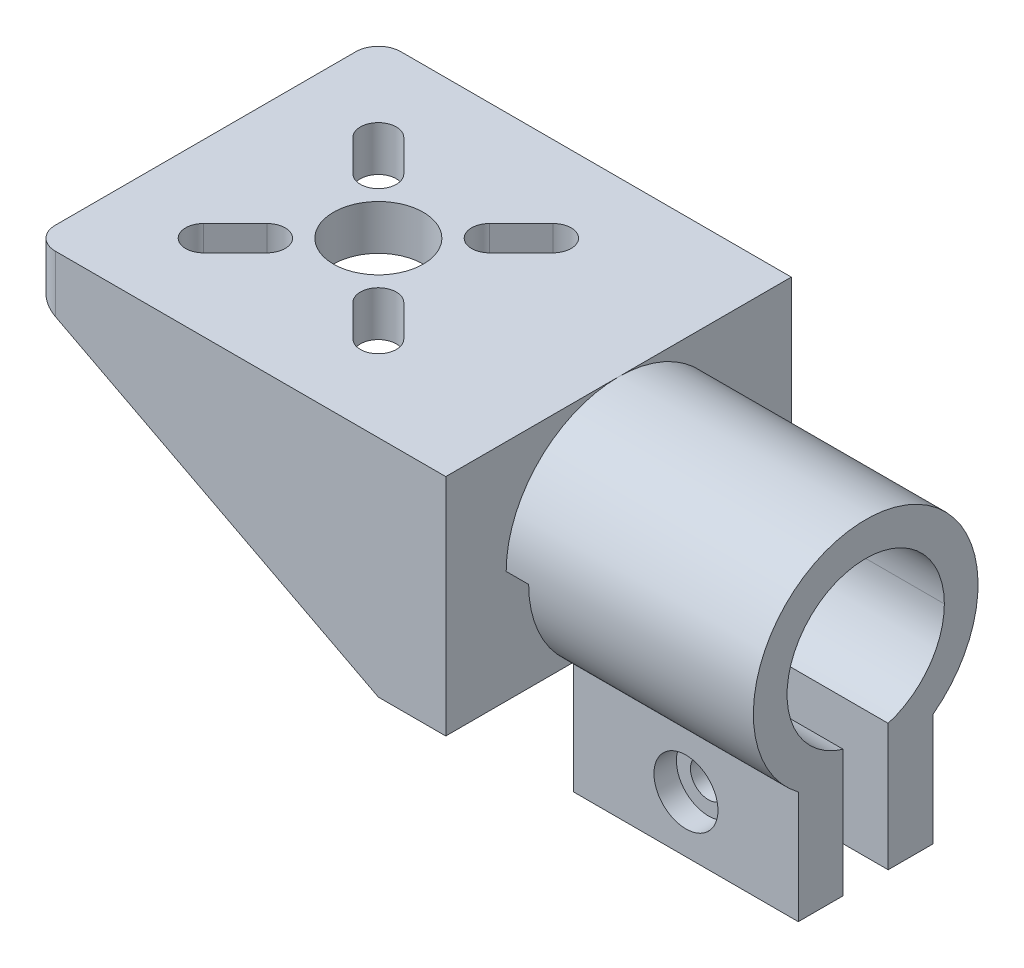
SolidWorks part; units mm, degrees
material "ABS"
ref_plane "Płaszczyzna przednia" through (0, 0, 0) normal (0, 0, 1) x (1, 0, 0)
ref_plane "Płaszczyzna górna" through (0, 0, 0) normal (0, 1, 0) x (1, 0, 0)
ref_plane "Płaszczyzna prawa" through (0, 0, 0) normal (1, 0, 0) x (0, 0, -1)
sketch "Szkic1" plane through (0, 0, 0) normal (0, 1, 0) x (1, 0, 0)
  line L0 (0, 0) -> (-4.9497, 4.9497) construction
  line L1 (-4.9497, 4.9497) -> (-7.7782, 7.7782) construction
  line L2 (-7.7782, 7.7782) -> (-4.9497, 4.9497) construction
  line L3 (-6.6468, 8.9095) -> (-3.8184, 6.0811)
  line L4 (-8.9095, 6.6468) -> (-6.0811, 3.8184)
  line L5 (7.7782, 7.7782) -> (4.9497, 4.9497) construction
  line L6 (8.9095, 6.6468) -> (6.0811, 3.8184)
  line L7 (6.6468, 8.9095) -> (3.8184, 6.0811)
  line L8 (7.7782, -7.7782) -> (4.9497, -4.9497) construction
  line L9 (6.6468, -8.9095) -> (3.8184, -6.0811)
  line L10 (8.9095, -6.6468) -> (6.0811, -3.8184)
  line L11 (-7.7782, -7.7782) -> (-4.9497, -4.9497) construction
  line L12 (-8.9095, -6.6468) -> (-6.0811, -3.8184)
  line L13 (-6.6468, -8.9095) -> (-3.8184, -6.0811)
  line L14 (0, 9) -> (0, -9) construction
  line L15 (-15.3782, 15.3782) -> (15.3782, 15.3782)
  line L16 (0, 0) -> (9.4723, 0) construction
  line L17 (-15.3782, -15.3782) -> (-15.3782, 15.3782)
  line L18 (15.3782, 15.3782) -> (15.3782, -15.3782)
  line L19 (15.3782, -15.3782) -> (-15.3782, -15.3782)
  circle A0 centre (0, 0) radius 4
  arc A10 (-6.6468, 8.9095) -> (-8.9095, 6.6468) centre (-7.7782, 7.7782) ccw
  arc A11 (-6.0811, 3.8184) -> (-3.8184, 6.0811) centre (-4.9497, 4.9497) ccw
  arc A12 (8.9095, 6.6468) -> (6.6468, 8.9095) centre (7.7782, 7.7782) ccw
  arc A13 (3.8184, 6.0811) -> (6.0811, 3.8184) centre (4.9497, 4.9497) ccw
  arc A14 (6.6468, -8.9095) -> (8.9095, -6.6468) centre (7.7782, -7.7782) ccw
  arc A15 (6.0811, -3.8184) -> (3.8184, -6.0811) centre (4.9497, -4.9497) ccw
  arc A16 (-8.9095, -6.6468) -> (-6.6468, -8.9095) centre (-7.7782, -7.7782) ccw
  arc A17 (-3.8184, -6.0811) -> (-6.0811, -3.8184) centre (-4.9497, -4.9497) ccw
  point P3 (-6.364, 6.364)
  point P13 (0, 0)
  point P14 (6.364, 6.364)
  point P21 (6.364, -6.364)
  point P22 (0, 0)
  point P29 (-6.364, -6.364)
  point P36 (0, 0)
  point P39 (0, -9)
  point P40 (0, 15.3782)
  point P45 (-15.3782, 0)
  dimension "D6" = 8
  dimension "D1" = 7
  dimension "D2" = 4
  dimension "D3" = 3.2
  dimension "D5" = 7.6
  dimension "D7" = 7.6
  dimension "D4" = 4
extrude "Dodanie-wyciągnięcie1" add sketch "Szkic1" along normal blind 4
ref_plane "Płaszczyzna1" through (15.3782, 0, 0) normal (1, 0, 0) x (0, 0, -1)
sketch "Szkic2" plane through (15.3782, 0, 0) normal (1, 0, 0) x (0, 0, -1)
  line L1 (0, -13) -> (0, -16) construction
  line L2 (-15.3782, -16) -> (15.3782, -16)
  line L3 (15.3782, -16) -> (15.3782, 4)
  line L4 (-15.3782, -16) -> (-15.3782, 4)
  line L8 (0, 4) -> (0, 1) construction
  line L9 (-15.3782, 4) -> (15.3782, 4) construction
  line L10 (-15.3782, 4) -> (15.3782, 4)
  circle A0 centre (0, -6) radius 7
  point P0 (0, -13)
  point P9 (0, -16)
  point P10 (0, -16)
  point P19 (0, 4)
  dimension "D1" = 14
  dimension "D2" = 3
  dimension "D3" = 3
extrude "Dodanie-wyciągnięcie2" add sketch "Szkic2" along normal blind 4 contours A0 | L4 L2 L3 A0 region at (15.3782, -6, 15.0113) region at (15.3782, -6, 0)
ref_plane "Płaszczyzna2" through (-3.2753, -6.2961, 0) normal (-0.4615, -0.8871, 0) x (-0.8871, 0.4615, 0)
sketch "Szkic5" plane through (-3.2753, -6.2961, 0) normal (-0.4615, -0.8871, 0) x (-0.8871, 0.4615, 0)
  line L0 (13.6426, -15.3782) -> (-21.0266, -15.3782)
  line L1 (-21.0266, -15.3782) -> (-21.0266, -12.3782)
  line L2 (-21.0266, -15.3782) -> (-21.0266, 15.3782) construction
  line L3 (-21.0266, -12.3782) -> (13.6426, -12.3782)
  line L4 (13.6426, 15.3782) -> (13.6426, -15.3782) construction
  line L5 (13.6426, -12.3782) -> (13.6426, -15.3782)
  dimension "D1" = 3
extrude "Dodanie-wyciągnięcie3" add sketch "Szkic5" against normal up to next
mirror "Lustro1" about plane through (0, 0, 0) normal (0, 0, 1) of "Dodanie-wyciągnięcie3"
extrude "Dodanie-wyciągnięcie4" add sketch "Szkic2<3>" along normal blind 2 from surface starting at face at (19.3782, -6, 0)
sketch "Szkic2<3>" plane through (15.3782, 0, 0) normal (1, 0, 0) x (0, 0, -1) same geometry as "Szkic2"
fillet "Zaokrąglenie4" radius 2 2 edges at (-15.3782, 2, 15.3782) (-15.3782, 2, -15.3782)
sketch "Szkic6" plane through (21.3782, 0, 0) normal (1, 0, 0) x (0, 0, -1)
  line L0 (-10, -6) -> (-7, -6)
  line L1 (-7, -6) -> (7, -6) construction
  line L2 (7, -6) -> (10, -6)
  line L3 (0, 4) -> (0, 1) construction
  line L4 (-15.3782, 4) -> (15.3782, 4) construction
  arc A0 (7, -6) -> (-7, -6) centre (0, -6) ccw
  arc A1 (10, -6) -> (-10, -6) centre (0, -6) ccw
  dimension "D3" = 3
  dimension "D2" = 7
extrude "Dodanie-wyciągnięcie5" add sketch "Szkic6" along normal blind 2
sketch "Szkic7" plane through (23.3782, 0, 0) normal (1, 0, 0) x (0, 0, -1)
  line L0 (0, -6) -> (0, -24) construction
  line L2 (2, -24) -> (2, -12.7082)
  line L3 (2, -24) -> (6, -24)
  line L4 (6, -24) -> (6, -14)
  line L5 (-2, -24) -> (-2, -12.7082)
  line L6 (-2, -24) -> (-6, -24)
  line L7 (-6, -24) -> (-6, -14)
  arc A0 (2, -12.7082) -> (-2, -12.7082) centre (0, -6) ccw
  arc A1 (6, -14) -> (-6, -14) centre (0, -6) ccw
  arc A2 (-2, -12.7082) -> (0, -13) centre (0, -6) ccw construction
  arc A3 (-2, -15.798) -> (0, -16) centre (0, -6) ccw construction
  arc A4 (0, -13) -> (2, -12.7082) centre (0, -6) ccw
  arc A5 (0, -16) -> (2, -15.798) centre (0, -6) ccw
  arc A6 (-6, -14) -> (-2, -15.798) centre (0, -6) ccw construction
  arc A7 (2, -15.798) -> (6, -14) centre (0, -6) ccw construction
  point P4 (0, 0)
  point P9 (0, -24)
  arc M3 (10, -6) -> (-10, -6) centre (0, -6) ccw
  line M4 (-10, -6) -> (-7, -6)
  arc M5 (-7, -6) -> (7, -6) centre (0, -6) cw
  line M6 (7, -6) -> (10, -6)
  dimension "D2" = 4
  dimension "D6" = 7
  dimension "D1" = 4
  dimension "D3" = 4
  dimension "D4" = 18
  dimension "D5" = 3
  dimension "D7" = 2
extrude "Dodanie-wyciągnięcie6" add sketch "Szkic7" along normal blind 20 contours M6 M3 M4 M5 | A1 L7 L6 L5 A0 M4 | L4 A1 A0 L2 L3 M6 region at (23.3782, -15.3369, -5.1379) region at (23.3782, 1.2236, 0) region at (23.3782, -15.3369, 5.1379)
sketch "Szkic8" plane through (19.3782, 0, 0) normal (1, 0, 0) x (0, 0, -1)
  line L0 (-4.9, -5.9447) -> (4.9, -5.9447) construction
  line L1 (4.9, -9.4447) -> (4.9, -2.4447)
  line L2 (4.9, -2.4447) -> (-4.9, -2.4447)
  line L3 (-4.9, -9.4447) -> (-4.9, -2.4447)
  line L4 (-4.9, -9.4447) -> (4.9, -9.4447)
  line L5 (0, 0) -> (0, -14.6269) construction
  point P4 (0, -5.9447)
  point P7 (4.9, -5.9447)
  point P9 (0, -5.9447)
  point P11 (-4.9, -5.9447)
  dimension "D2" = 7
  dimension "D1" = 9.8
extrude "Wytnij-wyciągnięcie1" cut sketch "Szkic8" against normal up to next
fillet "Zaokrąglenie5" radius 4 4 edges at (17.3782, -2.4447, 4.9) (17.3782, -2.4447, -4.9) (17.3782, -9.4447, -4.9) (17.3782, -9.4447, 4.9)
sketch "Szkic9" plane through (0, 0, 6) normal (0, 0, 1) x (1, 0, 0)
  line L0 (23.3782, -19) -> (43.3782, -19) construction
  line L1 (23.3782, -24) -> (43.3782, -24) construction
  line L2 (23.3782, -24) -> (23.3782, -14) construction
  line L3 (23.3782, -14) -> (43.3782, -14) construction
  line L4 (43.3782, -24) -> (43.3782, -14) construction
  circle A0 centre (33.3782, -19) radius 1.6
  dimension "D1" = 3.2
extrude "Wytnij-wyciągnięcie2" cut sketch "Szkic9" against normal up to surface (12 mm away) up to face at (33.3782, -19, -6)
sketch "Szkic10" plane through (0, 0, 6) normal (0, 0, 1) x (1, 0, 0)
  circle A0 centre (33.3782, -19) radius 2.85
  dimension "D1" = 5.7
extrude "Wytnij-wyciągnięcie3" cut sketch "Szkic10" against normal blind 2
sketch "Szkic11" plane through (0, 0, -6) normal (0, 0, -1) x (-1, 0, 0)
  line L1 (-36.6691, -19) -> (-35.0236, -21.85)
  line L2 (-35.0236, -21.85) -> (-31.7327, -21.85)
  line L3 (-31.7327, -21.85) -> (-30.0873, -19)
  line L4 (-30.0873, -19) -> (-31.7327, -16.15)
  line L5 (-31.7327, -16.15) -> (-35.0236, -16.15)
  line L6 (-35.0236, -16.15) -> (-36.6691, -19)
  circle A0 centre (-33.3782, -19) radius 2.85 construction
  dimension "D1" = 5.7
extrude "Wytnij-wyciągnięcie4" cut sketch "Szkic11" against normal blind 2
equation "\"Diameter\"=14"
equation "\"WallThickness\"= 3"
equation "\"D5@Szkic1\"=1.6 +\"WallThickness\"*2"
equation "\"D7@Szkic1\"=1.6 +\"WallThickness\"*2"
equation "\"D2@Szkic2\"=\"WallThickness\""
equation "\"D1@Szkic5\"=\"WallThickness\""
equation "\"Tolerance\"= 0.1"
equation "\"SkrewGap\"= 4"
equation "\"SkrewWallThickness\"= 4"
equation "\"SkrewLength\"= 8"
equation "\"D1@Szkic7\"=\"SkrewGap\""
equation "\"D2@Szkic7\"=\"SkrewWallThickness\""
equation "\"D3@Szkic7\"=\"SkrewWallThickness\""
equation "\"D4@Szkic7\"=\"Diameter\"/2 +\"WallThickness\" +\"SkrewLength\""
equation "\"D5@Szkic7\"=\"WallThickness\""
equation "\"D3@Szkic2\"=\"WallThickness\""
equation "\"D2@Szkic6\"=\"Diameter\"/2"
equation "\"D3@Szkic6\"=\"WallThickness\""
equation "\"D6@Szkic7\"=\"Diameter\"/2"
equation "\"D7@Szkic7\"=\"SkrewGap\"/2"
equation "\"D1@Szkic6\"=\"WallThickness\""
equation "\"D1@Szkic2\"=\"Diameter\""
equation "\"D1@Szkic8\"=\"Diameter\"*0.7"
equation "\"D2@Szkic8\"=\"Diameter\"*0.5"
equation "\"D1@Szkic9\"=3 +\"Tolerance\"*2"
equation "\"D1@Szkic10\"=5.5 +\"Tolerance\"*2"
equation "\"D1@Wytnij-wyciągnięcie3\"=\"SkrewWallThickness\"/2"
equation "\"D1@Szkic11\"=5.5 +\"Tolerance\"*2"
equation "\"D1@Wytnij-wyciągnięcie4\"=\"SkrewWallThickness\"/2"
